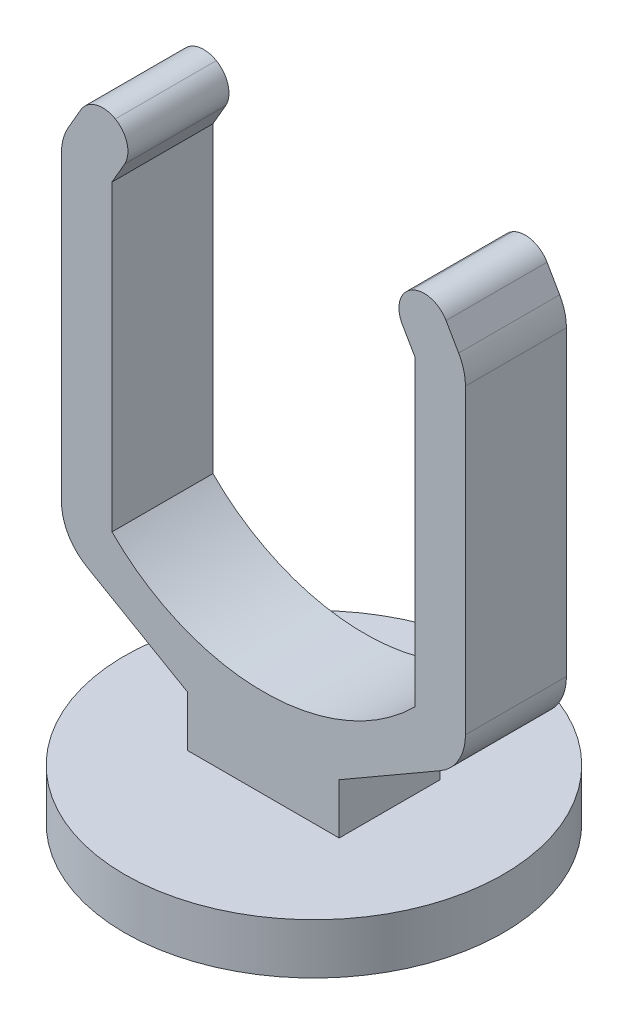
SolidWorks part; units mm, degrees
ref_plane "前视基准面" through (0, 0, 0) normal (0, 0, 1) x (1, 0, 0)
ref_plane "上视基准面" through (0, 0, 0) normal (0, 1, 0) x (1, 0, 0)
ref_plane "右视基准面" through (0, 0, 0) normal (1, 0, 0) x (0, 0, -1)
other "Configuration Table"
sketch "草图1" plane through (0, 0, 0) normal (0, 1, 0) x (1, 0, 0)
  circle A0 centre (0, 0) radius 37.5
  dimension "D1" = 75
extrude "凸台-拉伸1" add sketch "草图1" along normal blind 10
sketch "草图2" plane through (0, 0, 0) normal (0, 0, 1) x (1, 0, 0)
  line L0 (15, 0) -> (15, 20)
  line L1 (-37.5, 0) -> (37.5, 0) construction
  line L2 (15, 20) -> (40, 34.4338)
  line L3 (40, 34.4338) -> (40, 102.6795)
  line L4 (40, 102.6795) -> (33.6603, 113.6603)
  line L5 (33.6603, 113.6603) -> (25, 108.6603)
  line L6 (25, 108.6603) -> (30, 100)
  line L7 (30, 100) -> (30, 40)
  line L8 (-30, 40) -> (-30, 100)
  line L9 (-30, 100) -> (-25, 108.6603)
  line L10 (-25, 108.6603) -> (-33.6603, 113.6603)
  line L11 (-33.6603, 113.6603) -> (-40, 102.6795)
  line L12 (-40, 102.6795) -> (-40, 34.4338)
  line L13 (-40, 34.4338) -> (-15, 20)
  line L14 (-15, 20) -> (-15, 0)
  line L15 (-15, 0) -> (15, 0)
  arc A0 (-30, 40) -> (30, 40) centre (0, 70) ccw
  point P1 (0, 0)
  point P21 (0, 0)
  dimension "D2" = 30
  dimension "D3" = 15
  dimension "D4" = 15
  dimension "D5" = 20
  dimension "D6" = 20
  dimension "D7" = 120
  dimension "D8" = 120
  dimension "D9" = 30
  dimension "D10" = 30
  dimension "D11" = 30
  dimension "D12" = 30
  dimension "D13" = 150
  dimension "D14" = 150
  dimension "D15" = 10
  dimension "D16" = 10
  dimension "D17" = 10
  dimension "D18" = 10
  dimension "D19" = 10
  dimension "D20" = 10
  dimension "D21" = 70
extrude "凸台-拉伸2" add sketch "草图2" along normal blind 10 and the other way blind 10
fillet "圆角1" radius 5 4 edges at (33.6603, 113.6603, 0) (25, 108.6603, 0) (-25, 108.6603, 0) (-33.6603, 113.6603, 0)
fillet "圆角2" radius 10 4 edges at (40, 102.6795, 0) (40, 34.4338, 0) (-40, 34.4338, 0) (-40, 102.6795, 0)
